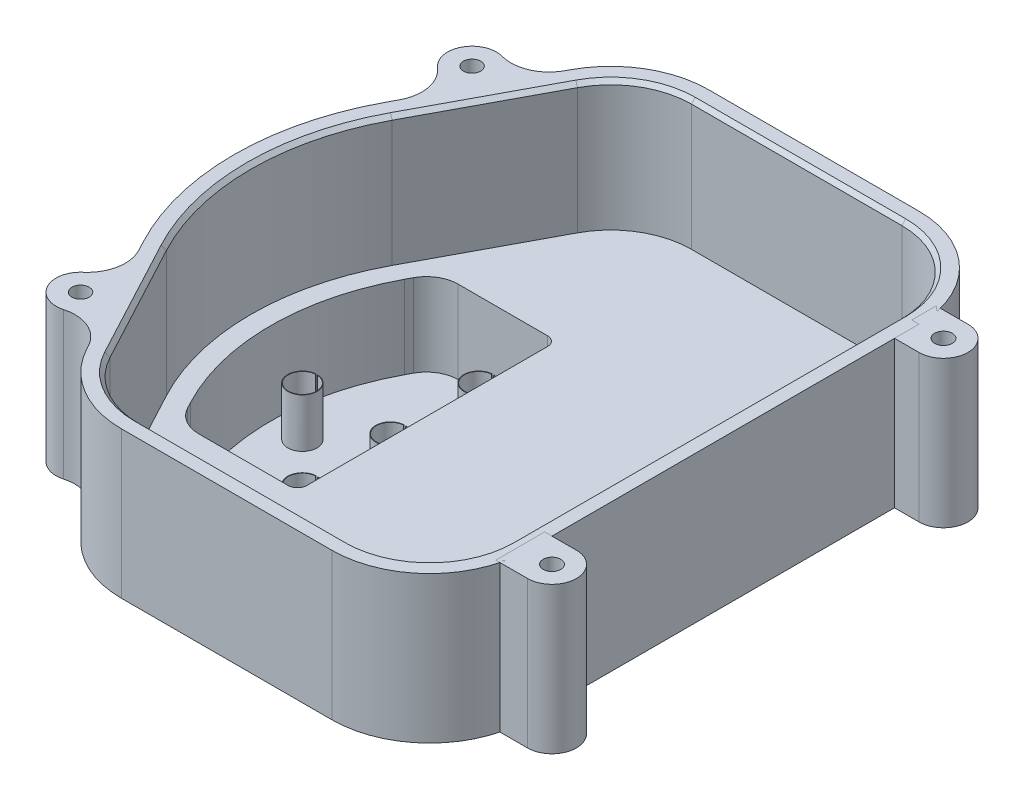
SolidWorks part; units mm, degrees
material "6061-T6 (SS)"
ref_plane "Front Plane" through (0, 0, 0) normal (0, 0, 1) x (1, 0, 0)
ref_plane "Top Plane" through (0, 0, 0) normal (0, 1, 0) x (1, 0, 0)
ref_plane "Right Plane" through (0, 0, 0) normal (1, 0, 0) x (0, 0, -1)
sketch "Sketch1" plane through (0, 0, 0) normal (0, 1, 0) x (1, 0, 0)
  line L0 (-57.15, 0) -> (-57.15, -50000) construction
  line L1 (-25.4, -76.2) -> (-25.4, -101.6) construction
  line L2 (-25.4, -76.2) -> (69.85, -76.2)
  line L3 (-25.4, 76.2) -> (69.85, 76.2)
  line L4 (69.85, -76.2) -> (69.85, 76.2)
  line L5 (-25.4, 76.2) -> (-25.4, 101.6) construction
  line L6 (0, 0) -> (0, -50000) construction
  line L7 (-49.3059, 31.3765) -> (-25.4, 76.2)
  line L8 (-57.15, 0) -> (69.85, 0) construction
  line L9 (-49.3059, -31.3765) -> (-25.4, -76.2)
  arc A0 (-49.3059, -31.3765) -> (-49.3059, 31.3765) centre (9.525, 0) cw
  point P0 (0, 0)
  dimension "D5" = 50.8
  dimension "D1" = 76.2
  dimension "D2" = 25.4
  dimension "D3" = 25.4
  dimension "D4" = 69.85
  dimension "D6" = 127
extrude "Boss-Extrude1" add sketch "Sketch1" along normal blind 38.1
fillet "Fillet1" radius 25.4 4 edges at (-25.4, 19.05, 76.2) (69.85, 19.05, 76.2) (69.85, 19.05, -76.2) (-25.4, 19.05, -76.2)
shell "Shell1" thickness 4.445 removed face at (4.3477, 38.1, 0)
sketch "Sketch13" plane through (0, 0, 0) normal (0, -1, 0) x (1, 0, 0)
  line L0 (0, 0) -> (-50000, 0) construction
  line L1 (-2.54, 38.1) -> (-2.54, -38.1)
  line L2 (-2.54, 38.1) -> (-40.2167, 38.1)
  line L3 (-49.3059, 31.3765) -> (-32.5718, 62.7529) construction
  line L4 (-40.2167, -38.1) -> (-2.54, -38.1)
  line L12 (-40.2167, -38.1) -> (-44.5994, -29.8824)
  line L13 (-44.5994, 29.8824) -> (-40.2167, 38.1)
  arc A1 (-49.3059, 31.3765) -> (-49.3059, -31.3765) centre (9.525, 0) ccw construction
  arc A5 (-44.5994, 29.8824) -> (-44.5994, -29.8824) centre (11.43, 0) ccw
  dimension "D3" = 49.53
  dimension "D2" = 63.5
  dimension "D5" = 54.61
  dimension "D1" = 76.2
extrude "nub" add sketch "Sketch13" along normal blind 23.368
fillet "Fillet2" radius 12.7 2 edges at (-40.2167, -11.684, -38.1) (-40.2167, -11.684, 38.1)
fillet "Fillet3" radius 6.858 2 edges at (-2.54, -11.684, -38.1) (-2.54, -11.684, 38.1)
sketch "Sketch8" plane through (0, 4.445, 0) normal (0, 1, 0) x (1, 0, 0)
  line L24 (-6.985, -31.242) -> (-6.985, 31.242)
  line L25 (-32.5967, -33.655) -> (-9.398, -33.655)
  line L26 (-40.6774, -27.7906) -> (-39.8805, -29.2847)
  line L27 (-39.8805, 29.2847) -> (-40.6774, 27.7906)
  line L28 (-32.5967, -33.655) -> (-9.398, -33.655)
  line L29 (-6.985, -31.242) -> (-6.985, 31.242)
  line L30 (-9.398, 33.655) -> (-32.5967, 33.655)
  line L31 (-40.6774, -27.7906) -> (-39.8805, -29.2847)
  line L32 (-39.8805, 29.2847) -> (-40.6774, 27.7906)
  line L33 (-9.398, 33.655) -> (-32.5967, 33.655)
  arc A30 (-6.985, 31.242) -> (-9.398, 33.655) centre (-9.398, 31.242) ccw
  arc A31 (-6.985, 31.242) -> (-9.398, 33.655) centre (-9.398, 31.242) ccw
  arc A32 (-40.6774, 27.7906) -> (-40.6774, -27.7906) centre (11.43, 0) ccw
  arc A33 (-39.8805, -29.2847) -> (-32.5967, -33.655) centre (-32.5967, -25.4) ccw
  arc A34 (-39.8805, -29.2847) -> (-32.5967, -33.655) centre (-32.5967, -25.4) ccw
  arc A35 (-32.5967, 33.655) -> (-39.8805, 29.2847) centre (-32.5967, 25.4) ccw
  arc A36 (-32.5967, 33.655) -> (-39.8805, 29.2847) centre (-32.5967, 25.4) ccw
  arc A37 (-40.6774, 27.7906) -> (-40.6774, -27.7906) centre (11.43, 0) ccw
  arc A38 (-9.398, -33.655) -> (-6.985, -31.242) centre (-9.398, -31.242) ccw
  arc A39 (-9.398, -33.655) -> (-6.985, -31.242) centre (-9.398, -31.242) ccw
  dimension "D1" = 4.445
extrude "Cut-Extrude1" cut sketch "Sketch8" against normal offset from surface (21.463 mm away) 6.35 up to face at (-27.2365, -23.368, 0)
chamfer "Chamfer1" distance 1.016 angle 45 10 edges at (-37.0168, 38.1, 44.9729) (-20.9413, 38.1, 68.7688) (-52.705, 38.1, 0) (17.145, 38.1, 71.755) (-37.0168, 38.1, -44.9729) (59.2674, 38.1, 65.6174) (-20.9413, 38.1, -68.7688) (65.405, 38.1, 0) (17.145, 38.1, -71.755) (59.2674, 38.1, -65.6174)
sketch "Sketch10" plane through (0, 38.1, 0) normal (0, 1, 0) x (1, 0, 0)
  line L0 (69.85, 47.625) -> (69.85, 15.875)
  line L1 (69.85, -50.8) -> (69.85, 50.8) construction
  line L2 (0, 0) -> (50000, 0) construction
  line L3 (69.85, -47.625) -> (69.85, -15.875)
  line L4 (-33.0698, 61.8191) -> (-48.011, 33.8044)
  line L5 (-32.5718, 62.7529) -> (-49.3059, 31.3765) construction
  line L6 (-44.4579, 56.9222) -> (-50.2886, 45.9897) construction
  line L7 (-42.0859, 47.888) -> (40559.6261, -29092.0967) construction
  line L8 (-44.4579, -56.9222) -> (-50.2886, -45.9897) construction
  line L9 (-33.0698, -61.8191) -> (-48.011, -33.8044)
  arc A0 (69.85, 47.625) -> (77.5939, 37.9451) centre (79.7719, 47.625) ccw
  arc A1 (77.5939, 37.9451) -> (77.5939, 25.5549) centre (76.2, 31.75) cw
  arc A2 (77.5939, -25.5549) -> (69.85, -15.875) centre (79.7719, -15.875) cw
  arc A3 (77.5939, 25.5549) -> (69.85, 15.875) centre (79.7719, 15.875) ccw
  arc A4 (77.5939, -37.9451) -> (77.5939, -25.5549) centre (76.2, -31.75) ccw
  arc A5 (69.85, -47.625) -> (77.5939, -37.9451) centre (79.7719, -47.625) cw
  arc A6 (-33.0698, 61.8191) -> (-44.4579, 56.9222) centre (-41.8244, 66.4882) cw
  arc A7 (-44.4579, 56.9222) -> (-50.2886, 45.9897) centre (-46.1433, 50.8) ccw
  arc A8 (-50.2886, 45.9897) -> (-48.011, 33.8044) centre (-56.7656, 38.4735) cw
  arc A9 (-50.2886, -45.9897) -> (-48.011, -33.8044) centre (-56.7656, -38.4735) ccw
  arc A10 (-44.4579, -56.9222) -> (-50.2886, -45.9897) centre (-46.1433, -50.8) cw
  arc A11 (-33.0698, -61.8191) -> (-44.4579, -56.9222) centre (-41.8244, -66.4882) ccw
  point P30 (-40.9388, 47.0647)
  dimension "D1" = 6.35
  dimension "D6" = 6.35
  dimension "D2" = 31.75
  dimension "D3" = 6.35
  dimension "D4" = 31.75
  dimension "D5" = 31.75
  dimension "D7" = 6.35
  dimension "D8" = 50.8
extrude "Boss-Extrude2" add sketch "Sketch10" against normal up to surface (38.1 mm away) up to face at (4.3477, 0, 0)
hole_wizard "#8 Clearance Hole1" positions "Sketch12" profile "Sketch11" hole size "#8" standard "Ansi Inch" end condition through all
sketch "Sketch12" plane through (0, 38.1, 0) normal (0, 1, 0) x (-1, 0, 0)
  arc A0 (44.4579, -56.9222) -> (50.2886, -45.9897) centre (46.1433, -50.8) ccw construction
  arc A1 (50.2886, 45.9897) -> (44.4579, 56.9222) centre (46.1433, 50.8) ccw construction
  arc A2 (-77.5939, 37.9451) -> (-77.5939, 25.5549) centre (-76.2, 31.75) ccw construction
  arc A3 (-77.5939, -25.5549) -> (-77.5939, -37.9451) centre (-76.2, -31.75) ccw construction
  point P0 (46.1433, -50.8)
  point P1 (46.1433, 50.8)
  point P3 (-76.2, 31.75)
  point P5 (-76.2, -31.75)
sketch "Sketch11" plane through (-46.1433, 38.1, -50.8) normal (1, 0, 0) x (0, 0, 1)
  line L0 (0, 0) -> (0, 61.468)
  line L1 (0, 61.468) -> (2.2479, 61.468)
  line L2 (2.2479, 61.468) -> (2.2479, 0)
  line L5 (2.2479, 0) -> (0, 0)
  line L11 (0, -6.35) -> (0, 107.95) construction
  dimension "Thru Hole Dia." = 4.4958
  dimension "Thru Hole Depth" = 61.468
sketch "Sketch14" plane through (0, -23.368, 0) normal (0, -1, 0) x (1, 0, 0)
  line L0 (0, 0) -> (50000, 0) construction
  line L1 (-2.54, -31.242) -> (-2.54, 31.242) construction
  circle A0 centre (-16.51, 22.86) radius 3.675
  circle A1 centre (-16.51, 0) radius 3.675
  circle A2 centre (-16.51, -22.86) radius 3.675
  circle A3 centre (-39.37, 0) radius 3.675
  dimension "D1" = 7.35
  dimension "D2" = 45.72
  dimension "D3" = 22.86
  dimension "D4" = 13.97
extrude "Cut-Extrude2" cut sketch "Sketch14" against normal through all
ref_point "Point1"
ref_plane "Plane1" through (-16.51, 0, 0) normal (-1, 0, 0) x (0, 0, 1)
ref_point "Point2"
ref_point "Point3"
ref_point "Point4"
sketch "Sketch16" plane through (0, -17.018, 0) normal (0, 1, 0) x (1, 0, 0)
  circle A0 centre (-16.51, -22.86) radius 3.6754
  circle A1 centre (-16.51, -22.86) radius 3.8024
  dimension "D1" = 7.3508
  dimension "D2" = 7.6048
extrude "Boss-Extrude3" add sketch "Sketch16" along normal blind 12.7
ref_plane "Plane2" through (0, 0, 19.0576) normal (0, 0, -1) x (-1, 0, 0)
sketch "Sketch17" plane through (0, 0, 19.0576) normal (0, 0, -1) x (-1, 0, 0)
  line L0 (20.3124, -4.318) -> (12.7076, -4.318) construction
  line L1 (16.256, -4.318) -> (16.256, -11.938)
  line L2 (16.764, -4.318) -> (16.764, -11.938)
  line L3 (16.256, -11.938) -> (16.764, -11.938)
  line L4 (16.256, -4.318) -> (16.764, -4.318)
  point P0 (16.51, -4.318)
  point P3 (16.764, -4.318)
  point P5 (16.256, -4.318)
  dimension "D1" = 0.254
  dimension "D2" = 0.254
  dimension "D3" = 7.62
extrude "Cut-Extrude4" cut sketch "Sketch17" against normal blind 2.54 contours L1 L3 L2 L4
pattern_linear "LPattern1" count 3 spacing 22.86 along (0, 0, -1) count 2 spacing 22.86 along (-1, 0, 0) skipping (0, 1), (2, 1) of "Boss-Extrude3", "Cut-Extrude4"
sketch "Sketch18" plane through (0, 38.1, 0) normal (0, 1, 0) x (1, 0, 0)
  line L1 (69.85, 47.625) -> (87.7506, 47.625)
  line L2 (69.85, 47.625) -> (69.85, -51.2029)
  line L3 (69.85, -51.2029) -> (87.7506, -51.2029)
  line L4 (87.7506, 47.625) -> (87.7506, -51.2029)
  dimension "D1" = 17.9006
  dimension "D2" = 98.8279
extrude "Cut-Extrude5" cut sketch "Sketch18" against normal through all
sketch "Sketch19" plane through (0, 38.1, 0) normal (0, 1, 0) x (1, 0, 0)
  line L0 (69.85, -50.8) -> (69.85, 50.8) construction
  line L1 (0, 0) -> (115.4293, 0) construction
  line L3 (76.2, 57.15) -> (67.9646, 57.15)
  line L4 (67.9646, 57.15) -> (67.9646, 44.45)
  line L5 (67.9646, 44.45) -> (76.2, 44.45)
  line L6 (67.9646, -44.45) -> (76.2, -44.45)
  line L7 (67.9646, -57.15) -> (67.9646, -44.45)
  line L8 (76.2, -57.15) -> (67.9646, -57.15)
  arc A0 (76.2, 44.45) -> (76.2, 57.15) centre (76.2, 50.8) ccw
  circle A1 centre (76.2, 50.8) radius 2.286
  circle A5 centre (76.2, -50.8) radius 2.286
  arc A6 (76.2, -44.45) -> (76.2, -57.15) centre (76.2, -50.8) cw
  point P4 (69.85, 0)
  dimension "D1" = 12.7
  dimension "D4" = 4.572
  dimension "D2" = 6.35
  dimension "D3" = 50.8
  dimension "D5" = 8.2354
extrude "Boss-Extrude4" add sketch "Sketch19" against normal up to surface (38.1 mm away) separate body up to face at (-17.274, 0, 0)
